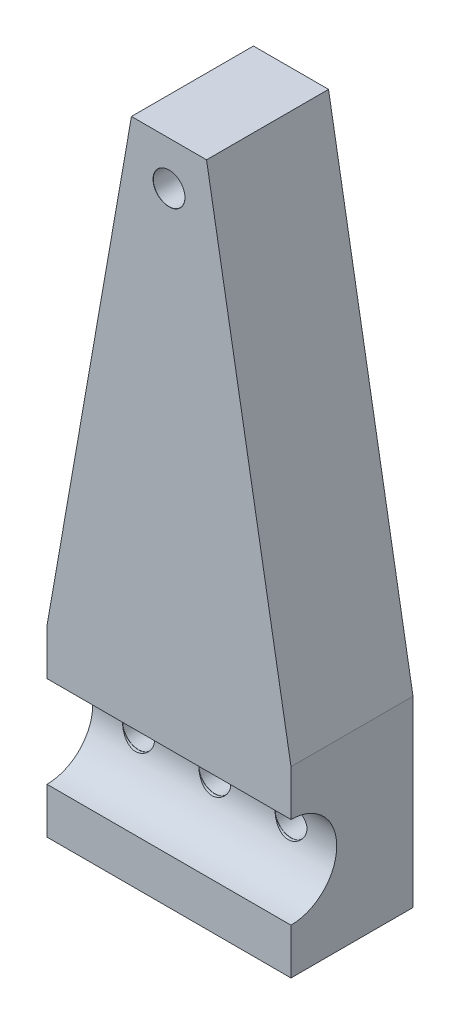
SolidWorks part; units mm, degrees
ref_plane "Front Plane" through (0, 0, 0) normal (0, 0, 1) x (1, 0, 0)
ref_plane "Top Plane" through (0, 0, 0) normal (0, 1, 0) x (1, 0, 0)
ref_plane "Right Plane" through (0, 0, 0) normal (1, 0, 0) x (0, 0, -1)
sketch "Sketch1" plane through (0, 0, 0) normal (0, 0, 1) x (1, 0, 0)
  line L0 (-25.4, 19.05) -> (-7.8164, 119.6762)
  line L1 (25.4, -19.05) -> (-25.4, -19.05)
  line L2 (25.4, -19.05) -> (25.4, 19.05)
  line L3 (25.4, 19.05) -> (-25.4, 19.05)
  line L4 (-25.4, -19.05) -> (-25.4, 19.05)
  line L5 (25.4, -19.05) -> (-25.4, 19.05) construction
  line L6 (25.4, 19.05) -> (-25.4, -19.05) construction
  line L7 (-7.8164, 119.6762) -> (7.8164, 119.6762)
  line L8 (7.8164, 119.6762) -> (25.4, 19.05)
  line L9 (-15.875, 0) -> (15.875, 0) construction
  line L10 (0, 119.6762) -> (0, 110.6189) construction
  point P0 (0, 0)
  point P8 (0, 119.6762)
  point P9 (0, 0)
  point P14 (7.8164, 119.6762)
  point P15 (0, 110.6189)
  dimension "D1" = 50.8
  dimension "D2" = 38.1
  dimension "D4" = 31.75
extrude "Boss-Extrude1" add sketch "Sketch1" along normal blind 25.4 contours L8 L7 L0 L3 | L4 L1 L2 L3 region at (0, 60.4851, 0) region at (0, 0, 0)
sketch "Sketch2" plane through (0, 0, 25.4) normal (0, 0, 1) x (1, 0, 0)
  line L0 (-25.4, 0) -> (25.4, 0)
  line L1 (-25.4, -19.05) -> (-25.4, 19.05) construction
  line L2 (25.4, -19.05) -> (25.4, 19.05) construction
sweep "Cut-Sweep1" cut path "Sketch2" circular profile diameter 19.05 parameters "D3"=19.05
hole_wizard "M6 Clearance Hole1" positions "3DSketch1" profile "Sketch9" hole size "M6" standard "ANSI Metric" end condition through all
sketch3d "3DSketch1"
  point P0 (0, 0, 15.875)
  point P4 (-15.875, 0, 15.875)
  point P6 (15.875, 0, 15.875)
  point P8 (0, 110.6189, 25.4)
  point P13 (0, 0, 0)
  point P14 (0, 0, 0)
sketch "Sketch9" plane through (0, 0, 15.875) normal (1, 0, 0) x (0, -1, 0)
  line L0 (0, 0) -> (0, 15.875)
  line L1 (0, 15.875) -> (3.3, 15.875)
  line L2 (3.3, 15.875) -> (3.3, 0.025)
  line L3 (3.3, 0.025) -> (3.325, 0)
  line L5 (3.325, 0) -> (0, 0)
  line L6 (-3.3, 0.025) -> (-3.325, 0) construction
  line L11 (0, -6.35) -> (0, 107.95) construction
  dimension "Thru Hole Dia." = 6.6
  dimension "Thru Hole Depth" = 15.875
  dimension "Near C'Sink Dia." = 6.65
  dimension "Near C'Sink Angle" = 90
equation "\"Rover_Length\"= 25in"
equation "\"Rover_Width\"= 18in"
equation "\"Rover_Height\"= 12in"
equation "\"Chassis_Wheelbase\"= 28in"
equation "\"Chassis_WheelDiam\"= 171mm"
equation "\"Chassis_ArmDiamWidth\"= 0.75in"
equation "\"Chassis_ArmAngle\"= 135deg"
equation "\"Chassis_ArmHeight\"= 8in"
equation "\"Chassis_HubMountOD\"= 3in"
equation "\"Chassis_WheelBoltHole\"= 36mm"
equation "\"Chassis_WheelBoltNum\"= 4"
equation "\"Chassis_DiffBarLength\"= 12in"
equation "\"Chassis_DiffBarWidth\"= 1in"
equation "\"Chassis_DiffBarHeight\"= 0.5in"
equation "\"Chassis_DiffLinkage_Length\"= 2.5in"
equation "\"Chassis_MountBracketThickness\"= 0.125in"
equation "\"Chassis_MountBracketWidth\"= 3in"
equation "\"Chassis_MountBacketOverlap\"= 0.5in"
equation "\"Chassis_ArmShaftDiam\"= 0.75in"
equation "\"Chassis_ArmHoleSpacing\" = 1.25in"
equation "\"D4@Sketch1\"=\"Chassis_ArmHoleSpacing\""
